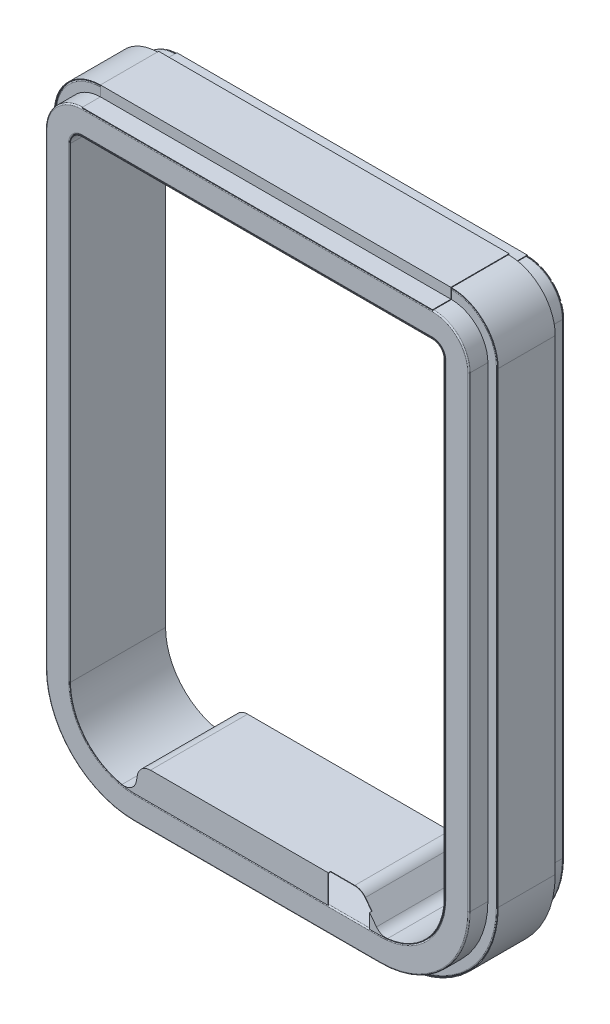
SolidWorks part; units mm, degrees
other "DetailItem1"
other "DetailItem2"
ref_plane "Front" through (0, 0, 0) normal (0, 0, 1) x (1, 0, 0)
ref_plane "Top" through (0, 0, 0) normal (0, 1, 0) x (1, 0, 0)
ref_plane "Right" through (0, 0, 0) normal (1, 0, 0) x (0, 0, -1)
sketch "Sketch15" plane through (0, 0, 0) normal (0, 0, 1) x (1, 0, 0)
  line L4 (3.9116, 60.0391) -> (3.9116, 11.1949)
  line L5 (41.8592, 61.3091) -> (5.1816, 61.3091)
  line L6 (43.1292, 11.1949) -> (43.1292, 60.0391)
  line L7 (10.6426, 4.4639) -> (36.3982, 4.4639)
  line L12 (1.3716, 11.1949) -> (1.3716, 60.0391)
  line L13 (36.3982, 1.9239) -> (10.6426, 1.9239)
  line L14 (45.6692, 60.0391) -> (45.6692, 11.1949)
  line L15 (5.1816, 63.8491) -> (41.8592, 63.8491)
  line L16 (23.5204, 61.3091) -> (23.5204, 4.4639) construction
  line L17 (23.5204, 32.8865) -> (13.0611, 32.8865) construction
  arc A4 (5.1816, 61.3091) -> (3.9116, 60.0391) centre (5.1816, 60.0391) ccw
  arc A5 (43.1292, 60.0391) -> (41.8592, 61.3091) centre (41.8592, 60.0391) ccw
  arc A6 (36.3982, 4.4639) -> (43.1292, 11.1949) centre (36.3982, 11.1949) ccw
  arc A7 (3.9116, 11.1949) -> (10.6426, 4.4639) centre (10.6426, 11.1949) ccw
  arc A12 (1.3716, 11.1949) -> (10.6426, 1.9239) centre (10.6426, 11.1949) ccw
  arc A13 (36.3982, 1.9239) -> (45.6692, 11.1949) centre (36.3982, 11.1949) ccw
  arc A14 (45.6692, 60.0391) -> (41.8592, 63.8491) centre (41.8592, 60.0391) ccw
  arc A15 (5.1816, 63.8491) -> (1.3716, 60.0391) centre (5.1816, 60.0391) ccw
  dimension "D1" = 1.27
  dimension "D2" = 6.731
  dimension "D3" = 2.54
  dimension "D4" = 23.5204
  dimension "D5" = 39.2176
  dimension "D6" = 56.8452
  dimension "D7" = 32.8865
extrude "Boss-Extrude4" add sketch "Sketch15" along normal blind 4.7244 and the other way blind 5.1816 separate body
ref_plane "Plane8" through (0, 0, 2.7432) normal (0, 0, 1) x (1, 0, 0)
sketch "Sketch16" plane through (0, 0, 2.7432) normal (0, 0, 1) x (1, 0, 0)
  line L8 (41.8592, 63.8491) -> (5.1816, 63.8491) construction
  line L9 (45.6692, 11.1949) -> (45.6692, 60.0391) construction
  line L10 (10.6426, 1.9239) -> (36.3982, 1.9239) construction
  line L11 (1.3716, 60.0391) -> (1.3716, 11.1949) construction
  line L12 (0.3556, 60.0391) -> (0.3556, 11.1949)
  line L13 (10.6426, 0.9079) -> (36.3982, 0.9079)
  line L14 (46.6852, 11.1949) -> (46.6852, 60.0391)
  line L15 (41.8592, 64.8651) -> (5.1816, 64.8651)
  line L16 (0.3556, 60.0391) -> (0.3556, 11.1949)
  line L17 (10.6426, 0.9079) -> (36.3982, 0.9079)
  line L18 (46.6852, 11.1949) -> (46.6852, 60.0391)
  line L19 (41.8592, 64.8651) -> (5.1816, 64.8651)
  line L20 (41.8592, 63.8491) -> (5.1816, 63.8491)
  line L21 (45.6692, 11.1949) -> (45.6692, 60.0391)
  line L22 (10.6426, 1.9239) -> (36.3982, 1.9239)
  line L23 (1.3716, 60.0391) -> (1.3716, 11.1949)
  arc A8 (45.6692, 60.0391) -> (41.8592, 63.8491) centre (41.8592, 60.0391) ccw construction
  arc A9 (36.3982, 1.9239) -> (45.6692, 11.1949) centre (36.3982, 11.1949) ccw construction
  arc A10 (1.3716, 11.1949) -> (10.6426, 1.9239) centre (10.6426, 11.1949) ccw construction
  arc A11 (5.1816, 63.8491) -> (1.3716, 60.0391) centre (5.1816, 60.0391) ccw construction
  arc A12 (5.1816, 64.8651) -> (0.3556, 60.0391) centre (5.1816, 60.0391) ccw
  arc A13 (0.3556, 11.1949) -> (10.6426, 0.9079) centre (10.6426, 11.1949) ccw
  arc A14 (36.3982, 0.9079) -> (46.6852, 11.1949) centre (36.3982, 11.1949) ccw
  arc A15 (46.6852, 60.0391) -> (41.8592, 64.8651) centre (41.8592, 60.0391) ccw
  arc A16 (5.1816, 64.8651) -> (0.3556, 60.0391) centre (5.1816, 60.0391) ccw
  arc A17 (0.3556, 11.1949) -> (10.6426, 0.9079) centre (10.6426, 11.1949) ccw
  arc A18 (36.3982, 0.9079) -> (46.6852, 11.1949) centre (36.3982, 11.1949) ccw
  arc A19 (46.6852, 60.0391) -> (41.8592, 64.8651) centre (41.8592, 60.0391) ccw
  arc A20 (45.6692, 60.0391) -> (41.8592, 63.8491) centre (41.8592, 60.0391) ccw
  arc A21 (36.3982, 1.9239) -> (45.6692, 11.1949) centre (36.3982, 11.1949) ccw
  arc A22 (1.3716, 11.1949) -> (10.6426, 1.9239) centre (10.6426, 11.1949) ccw
  arc A23 (5.1816, 63.8491) -> (1.3716, 60.0391) centre (5.1816, 60.0391) ccw
  dimension "D1" = 1.016
extrude "Boss-Extrude5" add sketch "Sketch16" against normal blind 5.969
fillet "Fillet1" radius 0.127 48 edges at (42.7572, 60.9372, -5.1816) (43.1292, 35.617, -5.1816) (41.1577, 6.4354, -5.1816) (23.5204, 4.4639, -5.1816) (5.8831, 6.4354, -5.1816) (3.9116, 35.617, -5.1816) (4.2836, 60.9372, -5.1816) (44.5533, 62.7332, -5.1816) (45.6692, 35.617, -5.1816) (42.9538, 4.6393, -5.1816) (23.5204, 1.9239, -5.1816) (4.087, 4.6393, -5.1816) (1.3716, 35.617, -5.1816) (2.4875, 62.7332, -5.1816) (45.2717, 63.4516, -3.2258) (46.6852, 35.617, -3.2258) (43.6722, 3.9209, -3.2258) (23.5204, 0.9079, -3.2258) (3.3686, 3.9209, -3.2258) (0.3556, 35.617, -3.2258) (1.7691, 63.4516, -3.2258) (45.2717, 63.4516, 2.7432) (46.6852, 35.617, 2.7432) (43.6722, 3.9209, 2.7432) (23.5204, 0.9079, 2.7432) (3.3686, 3.9209, 2.7432) (0.3556, 35.617, 2.7432) (1.7691, 63.4516, 2.7432) (42.7572, 60.9372, 4.7244) (43.1292, 35.617, 4.7244) (41.1577, 6.4354, 4.7244) (23.5204, 4.4639, 4.7244) (5.8831, 6.4354, 4.7244) (3.9116, 35.617, 4.7244) (4.2836, 60.9372, 4.7244) (44.5533, 62.7332, 4.7244) (45.6692, 35.617, 4.7244) (42.9538, 4.6393, 4.7244) (23.5204, 1.9239, 4.7244) (4.087, 4.6393, 4.7244) (1.3716, 35.617, 4.7244) (2.4875, 62.7332, 4.7244) (23.5204, 61.3091, -5.1816) (23.5204, 63.8491, -5.1816) (23.5204, 64.8651, -3.2258) (23.5204, 64.8651, 2.7432) (23.5204, 61.3091, 4.7244) (23.5204, 63.8491, 4.7244)
ref_plane "Plane1" through (0, 0, -1.8796) normal (0, 0, 1) x (1, 0, 0)
sketch "Sketch1" plane through (0, 0, -1.8796) normal (0, 0, 1) x (1, 0, 0)
  spline S0 degree 3 poles (23.5204, 0.7301) (4.8767, 0.6235) (10.288, 0.5536) (8.1184, 1.4309) knots 0 0 0 0 1 1 1 1
  dimension "D2" = 23.5204
ref_plane "Plane2" through (23.5204, 0.7301, -1.8796) normal (-1, -0.0057, 0) x (0, 0, 1)
sketch "Sketch2" plane through (23.5204, 0.7301, -1.8796) normal (-1, -0.0057, 0) x (0, 0, 1)
  line L2 (0.2921, -0.0762) -> (-0.2921, -0.0762)
  line L3 (0.2921, -0.0762) -> (0.2921, 0.0762)
  line L4 (0.2921, 0.0762) -> (-0.2921, 0.0762)
  line L5 (-0.2921, -0.0762) -> (-0.2921, 0.0762)
  line L6 (0.2921, -0.0762) -> (-0.2921, 0.0762) construction
  line L8 (0.2921, 0.0762) -> (-0.2921, -0.0762) construction
  point P0 (0, 0)
  dimension "D1" = 0.1524
  dimension "D2" = 0.5842
sweep "Sweep1" add profiles "Sketch2" path "Sketch1"
ref_plane "Plane5" [suppressed] through (33.274, 0, 0) normal (1, 0, 0) x (0, 0, -1)
ref_plane "Plane3" through (0, 0, -3.2512) normal (0, 0, 1) x (1, 0, 0)
sketch "Sketch3" plane through (0, 0, -3.2512) normal (0, 0, 1) x (1, 0, 0)
  line L3 (28.1912, 5.0643) -> (29.4725, 5.0643)
  arc A0 (29.4725, 5.0643) -> (31.7532, 4.7036) centre (29.4725, -2.3271) cw
  arc A1 (31.7532, 4.7036) -> (33.2691, 4.4639) centre (33.2691, 9.3766) ccw
ref_plane "Plane4" through (33.2691, 4.4639, -3.2512) normal (1, 0, 0) x (0, 0, -1)
sketch "Sketch4" plane through (33.2691, 0.758, 0.1016) normal (-1, 0, 0) x (0, 0, 1)
  line L1 (-3.6449, 3.7821) -> (-3.0607, 3.7821)
  line L2 (-3.6449, 3.7821) -> (-3.6449, 3.6297)
  line L3 (-3.6449, 3.6297) -> (-3.0607, 3.6297)
  line L4 (-3.0607, 3.7821) -> (-3.0607, 3.6297)
  line L5 (-3.6449, 3.7821) -> (-3.0607, 3.6297) construction
  line L6 (-3.6449, 3.6297) -> (-3.0607, 3.7821) construction
  point P0 (-3.3528, 3.7059)
  dimension "D1" = 0.5842
  dimension "D2" = 0.1524
sweep "Sweep2" add profiles "Sketch4" path "Sketch3"
sketch "Sketch6" [suppressed] plane through (0, 0, -5.0546) normal (0, 0, 1) x (1, 0, 0)
  line L0 (33.274, 4.4639) -> (32.3952, 4.4639)
  line L2 (29.0934, 7.7657) -> (29.0934, 8.5405)
  arc A0 (32.3952, 4.4639) -> (29.0934, 7.7657) centre (32.3952, 7.7657) cw
  dimension "D1" = 3.3018
sketch "Sketch7" [suppressed] plane through (33.274, 0, 0) normal (1, 0, 0) x (0, 0, -1)
  line L2 (5.0425, 4.3786) -> (4.4583, 4.3786)
  line L3 (5.0425, 4.3786) -> (5.0425, 4.531)
  line L4 (5.0425, 4.531) -> (4.4583, 4.531)
  line L5 (4.4583, 4.3786) -> (4.4583, 4.531)
  line L6 (5.0425, 4.3786) -> (4.4583, 4.531) construction
  line L7 (5.0425, 4.531) -> (4.4583, 4.3786) construction
  point P0 (4.7504, 4.4548)
  dimension "D1" = 0.5842
  dimension "D2" = 0.1524
sweep "Sweep4" [suppressed] add profiles "Sketch7" path "Sketch6"
sketch "Sketch8" [suppressed] plane through (0, 0, -1.8796) normal (0, 0, 1) x (1, 0, 0)
  line L0 (26.3291, -0.2377) -> (86.8426, -0.2377)
  arc A0 (10.6426, 0.9079) -> (13.2736, 0.7158) centre (10.643, -17.1973) cw
  arc A1 (13.2736, 0.7158) -> (26.3291, -0.2377) centre (26.3291, 89.6195) ccw
  dimension "D1" = 76.2
ref_plane "Plane6" [suppressed] through (10.6426, 0.9079, 2.6162) normal (1, 0, 0) x (0, 0, -1)
sketch "Sketch9" [suppressed] plane through (10.6426, 0.9079, 2.6162) normal (1, 0, 0) x (0, 0, -1)
  line L0 (5.715, -0.0006) -> (0, -0.0006) construction
  line L1 (1.5119, 0.2788) -> (0.9277, 0.2788)
  line L2 (1.5119, 0.2788) -> (1.5119, 0.1264)
  line L3 (1.5119, 0.1264) -> (0.9277, 0.1264)
  line L4 (0.9277, 0.2788) -> (0.9277, 0.1264)
  line L5 (1.5119, 0.2788) -> (0.9277, 0.1264) construction
  line L6 (1.5119, 0.1264) -> (0.9277, 0.2788) construction
  point P0 (1.2198, 0.2026)
  dimension "D1" = 0.5842
  dimension "D2" = 0.1524
  dimension "D3" = 0.2032
sweep "Sweep5" [suppressed] add profiles "Sketch9" path "Sketch8"
sketch "Sketch10" plane through (0, 0, 4.7244) normal (0, 0, 1) x (1, 0, 0)
  line L0 (12.3423, 7.4248) -> (33.4766, 7.4248)
  line L1 (10.9685, 6.2812) -> (10.6426, 4.5147)
  line L2 (36.3982, 4.5147) -> (34.585, 6.8781)
  line L3 (36.3731, 4.464) -> (34.5447, 6.8472)
  line L4 (12.3423, 7.374) -> (33.4766, 7.374)
  line L5 (11.0185, 6.272) -> (10.6849, 4.4641)
  line L6 (11.0185, 6.272) -> (10.6926, 4.5055) construction
  line L8 (41.8592, 61.3091) -> (5.1816, 61.3091) construction
  line L9 (43.1292, 11.1949) -> (43.1292, 60.0391) construction
  line L11 (3.9116, 60.0391) -> (3.9116, 11.1949) construction
  line L12 (3.9624, 60.0391) -> (3.9624, 11.1949)
  line L13 (10.6426, 4.5147) -> (36.3982, 4.5147)
  line L14 (43.0784, 11.1949) -> (43.0784, 60.0391)
  line L15 (41.8592, 61.2583) -> (5.1816, 61.2583)
  line L16 (3.9624, 60.0391) -> (3.9624, 11.1949)
  line L18 (43.0784, 11.1949) -> (43.0784, 60.0391)
  line L19 (41.8592, 61.2583) -> (5.1816, 61.2583)
  line L20 (41.8592, 61.3091) -> (5.1816, 61.3091)
  line L21 (43.1292, 11.1949) -> (43.1292, 60.0391)
  line L22 (36.3579, 4.4838) -> (34.5447, 6.8472) construction
  line L23 (3.9116, 60.0391) -> (3.9116, 11.1949)
  arc A0 (12.3423, 7.4248) -> (10.9685, 6.2812) centre (12.3423, 6.0278) ccw
  arc A1 (33.4766, 7.4248) -> (34.585, 6.8781) centre (33.4766, 6.0278) cw
  arc A2 (33.4766, 7.374) -> (34.5447, 6.8472) centre (33.4766, 6.0278) cw
  arc A3 (12.3423, 7.374) -> (11.0185, 6.272) centre (12.3423, 6.0278) ccw
  arc A8 (43.1292, 60.0391) -> (41.8592, 61.3091) centre (41.8592, 60.0391) ccw construction
  arc A9 (36.3982, 4.4639) -> (43.1292, 11.1949) centre (36.3982, 11.1949) ccw construction
  arc A10 (3.9116, 11.1949) -> (10.6426, 4.4639) centre (10.6426, 11.1949) ccw construction
  arc A11 (5.1816, 61.3091) -> (3.9116, 60.0391) centre (5.1816, 60.0391) ccw construction
  arc A12 (5.1816, 61.2583) -> (3.9624, 60.0391) centre (5.1816, 60.0391) ccw
  arc A13 (3.9624, 11.1949) -> (10.6426, 4.5147) centre (10.6426, 11.1949) ccw
  arc A14 (36.3982, 4.5147) -> (43.0784, 11.1949) centre (36.3982, 11.1949) ccw
  arc A15 (43.0784, 60.0391) -> (41.8592, 61.2583) centre (41.8592, 60.0391) ccw
  arc A16 (5.1816, 61.2583) -> (3.9624, 60.0391) centre (5.1816, 60.0391) ccw
  arc A17 (3.9624, 11.1949) -> (10.6426, 4.5147) centre (10.6426, 11.1949) ccw
  arc A18 (36.3982, 4.5147) -> (43.0784, 11.1949) centre (36.3982, 11.1949) ccw
  arc A19 (43.0784, 60.0391) -> (41.8592, 61.2583) centre (41.8592, 60.0391) ccw
  arc A20 (43.1292, 60.0391) -> (41.8592, 61.3091) centre (41.8592, 60.0391) ccw
  arc A21 (36.3731, 4.464) -> (43.1292, 11.1949) centre (36.3982, 11.1949) ccw
  arc A22 (3.9116, 11.1949) -> (10.6849, 4.4641) centre (10.6426, 11.1949) ccw
  arc A23 (5.1816, 61.3091) -> (3.9116, 60.0391) centre (5.1816, 60.0391) ccw
  dimension "D2" = 1.397
  dimension "D4" = 7.374
  dimension "D1" = 0.0508
  dimension "D3" = 0.0508
extrude "Boss-Extrude1" add sketch "Sketch10" against normal blind 9.906 separate body
sketch "Sketch11" plane through (0, 0, 2.7432) normal (0, 0, 1) x (1, 0, 0)
  line L8 (5.1816, 64.8651) -> (41.8592, 64.8651) construction
  line L9 (0.3556, 11.1949) -> (0.3556, 60.0391) construction
  line L10 (36.3982, 0.9079) -> (10.6426, 0.9079) construction
  line L11 (46.6852, 60.0391) -> (46.6852, 11.1949) construction
  line L12 (46.7487, 11.1949) -> (46.7487, 60.0391)
  line L13 (10.6426, 0.8444) -> (36.3982, 0.8444)
  line L14 (0.2921, 60.0391) -> (0.2921, 11.1949)
  line L15 (41.8592, 64.9286) -> (5.1816, 64.9286)
  line L16 (46.7487, 11.1949) -> (46.7487, 60.0391)
  line L17 (10.6426, 0.8444) -> (36.3982, 0.8444)
  line L18 (0.2921, 60.0391) -> (0.2921, 11.1949)
  line L19 (41.8592, 64.9286) -> (5.1816, 64.9286)
  line L20 (5.1816, 64.8651) -> (41.8592, 64.8651)
  line L21 (0.3556, 11.1949) -> (0.3556, 60.0391)
  line L22 (36.3982, 0.9079) -> (10.6426, 0.9079)
  line L23 (46.6852, 60.0391) -> (46.6852, 11.1949)
  arc A8 (5.1816, 64.8651) -> (0.3556, 60.0391) centre (5.1816, 60.0391) ccw construction
  arc A9 (0.3556, 11.1949) -> (10.6426, 0.9079) centre (10.6426, 11.1949) ccw construction
  arc A10 (36.3982, 0.9079) -> (46.6852, 11.1949) centre (36.3982, 11.1949) ccw construction
  arc A11 (46.6852, 60.0391) -> (41.8592, 64.8651) centre (41.8592, 60.0391) ccw construction
  arc A12 (46.7487, 60.0391) -> (41.8592, 64.9286) centre (41.8592, 60.0391) ccw
  arc A13 (36.3982, 0.8444) -> (46.7487, 11.1949) centre (36.3982, 11.1949) ccw
  arc A14 (0.2921, 11.1949) -> (10.6426, 0.8444) centre (10.6426, 11.1949) ccw
  arc A15 (5.1816, 64.9286) -> (0.2921, 60.0391) centre (5.1816, 60.0391) ccw
  arc A16 (46.7487, 60.0391) -> (41.8592, 64.9286) centre (41.8592, 60.0391) ccw
  arc A17 (36.3982, 0.8444) -> (46.7487, 11.1949) centre (36.3982, 11.1949) ccw
  arc A18 (0.2921, 11.1949) -> (10.6426, 0.8444) centre (10.6426, 11.1949) ccw
  arc A19 (5.1816, 64.9286) -> (0.2921, 60.0391) centre (5.1816, 60.0391) ccw
  arc A20 (5.1816, 64.8651) -> (0.3556, 60.0391) centre (5.1816, 60.0391) ccw
  arc A21 (0.3556, 11.1949) -> (10.6426, 0.9079) centre (10.6426, 11.1949) ccw
  arc A22 (36.3982, 0.9079) -> (46.6852, 11.1949) centre (36.3982, 11.1949) ccw
  arc A23 (46.6852, 60.0391) -> (41.8592, 64.8651) centre (41.8592, 60.0391) ccw
  dimension "D1" = 0.0635
extrude "Boss-Extrude2" add sketch "Sketch11" against normal blind 5.969 separate body
sketch "Sketch12" plane through (0, 0, -5.1816) normal (0, 0, -1) x (-1, 0, 0)
  line L0 (-10.6426, 4.5147) -> (-10.9685, 6.2812) construction
  line L1 (-12.3423, 7.4248) -> (-33.4766, 7.4248) construction
  line L2 (-34.585, 6.8781) -> (-36.3982, 4.5147) construction
  line L3 (-10.6426, 4.5147) -> (-10.9685, 6.2812)
  line L4 (-12.3423, 7.4248) -> (-33.4766, 7.4248)
  line L5 (-34.585, 6.8781) -> (-36.3982, 4.5147)
  line L7 (-13.6987, 3.3028) -> (-33.3421, 3.3028)
  line L8 (-41.8592, 61.2583) -> (-5.1816, 61.2583) construction
  line L9 (-43.0784, 11.1949) -> (-43.0784, 60.0391) construction
  line L11 (-3.9624, 60.0391) -> (-3.9624, 11.1949) construction
  line L16 (-1.4224, 11.1949) -> (-1.4224, 60.0391)
  line L17 (-36.3982, 1.9747) -> (-34.361, 1.9747)
  line L18 (-45.6184, 60.0391) -> (-45.6184, 11.1949)
  line L19 (-5.1816, 63.7983) -> (-41.8592, 63.7983)
  line L20 (-41.8592, 61.2583) -> (-5.1816, 61.2583)
  line L21 (-43.0784, 11.1949) -> (-43.0784, 60.0391)
  line L22 (-23.5204, 1.0349) -> (-23.5204, 4.8815) construction
  line L23 (-3.9624, 60.0391) -> (-3.9624, 11.1949)
  line L24 (-36.3982, 1.0349) -> (-10.6426, 1.0349) construction
  line L28 (-34.361, 1.9747) -> (-33.3421, 3.3028)
  line L29 (-12.6798, 1.9747) -> (-13.6987, 3.3028)
  line L30 (-10.6426, 1.9747) -> (-12.6798, 1.9747)
  arc A0 (-10.9685, 6.2812) -> (-12.3423, 7.4248) centre (-12.3423, 6.0278) ccw construction
  arc A1 (-33.4766, 7.4248) -> (-34.585, 6.8781) centre (-33.4766, 6.0278) ccw construction
  arc A2 (-10.9685, 6.2812) -> (-12.3423, 7.4248) centre (-12.3423, 6.0278) ccw
  arc A3 (-33.4766, 7.4248) -> (-34.585, 6.8781) centre (-33.4766, 6.0278) ccw
  arc A8 (-41.8592, 61.2583) -> (-43.0784, 60.0391) centre (-41.8592, 60.0391) ccw construction
  arc A9 (-43.0784, 11.1949) -> (-36.3982, 4.5147) centre (-36.3982, 11.1949) ccw construction
  arc A10 (-10.6426, 4.5147) -> (-3.9624, 11.1949) centre (-10.6426, 11.1949) ccw construction
  arc A11 (-3.9624, 60.0391) -> (-5.1816, 61.2583) centre (-5.1816, 60.0391) ccw construction
  arc A16 (-1.4224, 60.0391) -> (-5.1816, 63.7983) centre (-5.1816, 60.0391) ccw
  arc A17 (-10.6426, 1.9747) -> (-1.4224, 11.1949) centre (-10.6426, 11.1949) ccw
  arc A18 (-45.6184, 11.1949) -> (-36.3982, 1.9747) centre (-36.3982, 11.1949) ccw
  arc A19 (-41.8592, 63.7983) -> (-45.6184, 60.0391) centre (-41.8592, 60.0391) ccw
  arc A20 (-41.8592, 61.2583) -> (-43.0784, 60.0391) centre (-41.8592, 60.0391) ccw
  arc A21 (-43.0784, 11.1949) -> (-36.3982, 4.5147) centre (-36.3982, 11.1949) ccw
  arc A22 (-10.6426, 4.5147) -> (-3.9624, 11.1949) centre (-10.6426, 11.1949) ccw
  arc A23 (-3.9624, 60.0391) -> (-5.1816, 61.2583) centre (-5.1816, 60.0391) ccw
extrude "Boss-Extrude3" add sketch "Sketch12" along normal blind 0.254
sketch "Sketch13" plane through (0, 0, -5.4356) normal (0, 0, -1) x (-1, 0, 0)
  line L0 (-41.8592, 60.0391) -> (-42.9953, 63.6225)
  line L2 (-41.8592, 60.0391) -> (-43.2706, 63.5233)
  line L3 (-41.8592, 60.0391) -> (-44.3277, 62.8742)
  line L4 (-41.8592, 60.0391) -> (-44.4687, 62.7451)
  line L5 (-41.8592, 60.0391) -> (-45.3349, 61.4713)
  line L6 (-41.8592, 60.0391) -> (-45.4154, 61.2576)
  line L7 (-23.5204, 61.2583) -> (-23.5204, 43.5667) construction
  line L9 (-5.1816, 60.0391) -> (-1.6254, 61.2576)
  line L10 (-5.1816, 60.0391) -> (-1.7059, 61.4713)
  line L11 (-5.1816, 60.0391) -> (-2.5721, 62.7451)
  line L12 (-5.1816, 60.0391) -> (-2.7131, 62.8742)
  line L13 (-5.1816, 60.0391) -> (-3.7702, 63.5233)
  line L14 (-5.1816, 60.0391) -> (-4.0455, 63.6225)
  arc A0 (-41.8592, 63.7983) -> (-45.6184, 60.0391) centre (-41.8592, 60.0391) ccw construction
  arc A1 (-41.8592, 63.7983) -> (-45.6184, 60.0391) centre (-41.8592, 60.0391) ccw
  circle A4 centre (-41.8592, 60.0391) radius 1.3647
  circle A5 centre (-5.1816, 60.0391) radius 1.3647
  arc A6 (-5.1816, 63.7983) -> (-1.4224, 60.0391) centre (-5.1816, 60.0391) cw
extrude "Cut-Extrude1" cut sketch "Sketch13" against normal blind 0.254
ref_plane "Plane7" through (23.5204, 0, 0) normal (-1, 0, 0) x (0, 0, 1)
sketch "Sketch14" plane through (23.5204, 0.7301, 1.397) normal (-1, 0, 0) x (0, 0, 1)
  line L0 (-4.6228, 64.1985) -> (1.3462, 64.1985)
  line L1 (1.3462, 59.309) -> (1.3462, 64.1985) construction
  line L2 (1.3462, 64.1985) -> (1.3462, 63.119)
  line L4 (1.3462, 63.119) -> (3.2004, 63.119) construction
  line L5 (1.3462, 63.119) -> (3.3274, 63.119)
  line L6 (-4.6228, 64.1985) -> (-4.6228, 59.309) construction
  line L7 (-4.6228, 64.1985) -> (-4.6228, 63.119)
  line L8 (-4.6228, 63.119) -> (-6.5916, 63.119)
  line L11 (-4.6228, 64.1985) -> (1.3462, 64.1985) construction
extrude "Extrude-Thin1" add sketch "Sketch14" along normal mid plane 36.6776 separate body thin thin type one direction reverse wall 0.0635
fillet "Fillet2" [suppressed] radius 0.127
ref_plane "coil midplane" [suppressed] through (0, 32.8865, 0) normal (0, 1, 0) x (1, 0, 0)
sketch "Sketch17" [suppressed] plane through (0, 0, 4.7244) normal (0, 0, 1) x (1, 0, 0)
  line L0 (41.8592, 63.8491) -> (5.1816, 63.8491) construction
  line L1 (45.6692, 11.1949) -> (45.6692, 60.0391) construction
  line L2 (10.6426, 1.9239) -> (36.3982, 1.9239) construction
  line L3 (1.3716, 60.0391) -> (1.3716, 11.1949) construction
  line L4 (41.8592, 63.8491) -> (5.1816, 63.8491)
  line L5 (45.6692, 11.1949) -> (45.6692, 60.0391)
  line L6 (10.6426, 1.9239) -> (36.3982, 1.9239)
  line L7 (1.3716, 60.0391) -> (1.3716, 11.1949)
  arc A0 (45.6692, 60.0391) -> (41.8592, 63.8491) centre (41.8592, 60.0391) ccw construction
  arc A1 (36.3982, 1.9239) -> (45.6692, 11.1949) centre (36.3982, 11.1949) ccw construction
  arc A2 (1.3716, 11.1949) -> (10.6426, 1.9239) centre (10.6426, 11.1949) ccw construction
  arc A3 (5.1816, 63.8491) -> (1.3716, 60.0391) centre (5.1816, 60.0391) ccw construction
  arc A4 (45.6692, 60.0391) -> (41.8592, 63.8491) centre (41.8592, 60.0391) ccw
  arc A5 (36.3982, 1.9239) -> (45.6692, 11.1949) centre (36.3982, 11.1949) ccw
  arc A6 (1.3716, 11.1949) -> (10.6426, 1.9239) centre (10.6426, 11.1949) ccw
  arc A7 (5.1816, 63.8491) -> (1.3716, 60.0391) centre (5.1816, 60.0391) ccw
sketch "Sketch19" [suppressed] plane through (0, 0, 2.7432) normal (0, 0, 1) x (1, 0, 0)
  line L0 (5.1816, 64.8651) -> (41.8592, 64.8651) construction
  line L1 (0.3556, 11.1949) -> (0.3556, 60.0391) construction
  line L2 (36.3982, 0.9079) -> (10.6426, 0.9079) construction
  line L3 (46.6852, 60.0391) -> (46.6852, 11.1949) construction
  line L4 (5.1816, 64.8651) -> (41.8592, 64.8651)
  line L5 (0.3556, 11.1949) -> (0.3556, 60.0391)
  line L6 (36.3982, 0.9079) -> (10.6426, 0.9079)
  line L7 (46.6852, 60.0391) -> (46.6852, 11.1949)
  line L12 (5.1816, 64.7127) -> (41.8592, 64.7127)
  line L13 (0.508, 11.1949) -> (0.508, 60.0391)
  line L14 (36.3982, 1.0603) -> (10.6426, 1.0603)
  line L15 (46.5328, 60.0391) -> (46.5328, 11.1949)
  arc A0 (5.1816, 64.8651) -> (0.3556, 60.0391) centre (5.1816, 60.0391) ccw construction
  arc A1 (0.3556, 11.1949) -> (10.6426, 0.9079) centre (10.6426, 11.1949) ccw construction
  arc A2 (36.3982, 0.9079) -> (46.6852, 11.1949) centre (36.3982, 11.1949) ccw construction
  arc A3 (46.6852, 60.0391) -> (41.8592, 64.8651) centre (41.8592, 60.0391) ccw construction
  arc A4 (5.1816, 64.8651) -> (0.3556, 60.0391) centre (5.1816, 60.0391) ccw
  arc A5 (0.3556, 11.1949) -> (10.6426, 0.9079) centre (10.6426, 11.1949) ccw
  arc A6 (36.3982, 0.9079) -> (46.6852, 11.1949) centre (36.3982, 11.1949) ccw
  arc A7 (46.6852, 60.0391) -> (41.8592, 64.8651) centre (41.8592, 60.0391) ccw
  arc A12 (46.5328, 60.0391) -> (41.8592, 64.7127) centre (41.8592, 60.0391) ccw
  arc A13 (5.1816, 64.7127) -> (0.508, 60.0391) centre (5.1816, 60.0391) ccw
  arc A14 (0.508, 11.1949) -> (10.6426, 1.0603) centre (10.6426, 11.1949) ccw
  arc A15 (36.3982, 1.0603) -> (46.5328, 11.1949) centre (36.3982, 11.1949) ccw
  dimension "D1" = 0.1524
extrude "Cut-Extrude3" [suppressed] cut sketch "Sketch19" against normal through all
sketch "Sketch18" [suppressed] plane through (0, 0, 4.7244) normal (0, 0, 1) x (1, 0, 0)
  line L4 (45.6692, 11.1949) -> (45.6692, 60.0391) construction
  line L5 (10.6426, 1.9239) -> (36.3982, 1.9239) construction
  line L6 (1.3716, 60.0391) -> (1.3716, 11.1949) construction
  line L7 (41.8592, 63.8491) -> (5.1816, 63.8491) construction
  line L12 (45.6692, 11.1949) -> (45.6692, 60.0391)
  line L13 (10.6426, 1.9239) -> (36.3982, 1.9239)
  line L14 (1.3716, 60.0391) -> (1.3716, 11.1949)
  line L15 (41.8592, 63.8491) -> (5.1816, 63.8491)
  line L20 (41.8592, 63.6967) -> (5.1816, 63.6967)
  line L21 (1.524, 60.0391) -> (1.524, 11.1949)
  line L22 (10.6426, 2.0763) -> (36.3982, 2.0763)
  line L23 (45.5168, 11.1949) -> (45.5168, 60.0391)
  line L24 (41.8592, 63.6967) -> (5.1816, 63.6967)
  line L25 (1.524, 60.0391) -> (1.524, 11.1949)
  line L26 (10.6426, 2.0763) -> (36.3982, 2.0763)
  line L27 (45.5168, 11.1949) -> (45.5168, 60.0391)
  arc A4 (45.6692, 60.0391) -> (41.8592, 63.8491) centre (41.8592, 60.0391) ccw construction
  arc A5 (36.3982, 1.9239) -> (45.6692, 11.1949) centre (36.3982, 11.1949) ccw construction
  arc A6 (1.3716, 11.1949) -> (10.6426, 1.9239) centre (10.6426, 11.1949) ccw construction
  arc A7 (5.1816, 63.8491) -> (1.3716, 60.0391) centre (5.1816, 60.0391) ccw construction
  arc A12 (45.6692, 60.0391) -> (41.8592, 63.8491) centre (41.8592, 60.0391) ccw
  arc A13 (36.3982, 1.9239) -> (45.6692, 11.1949) centre (36.3982, 11.1949) ccw
  arc A14 (1.3716, 11.1949) -> (10.6426, 1.9239) centre (10.6426, 11.1949) ccw
  arc A15 (5.1816, 63.8491) -> (1.3716, 60.0391) centre (5.1816, 60.0391) ccw
  arc A20 (5.1816, 63.6967) -> (1.524, 60.0391) centre (5.1816, 60.0391) ccw
  arc A21 (1.524, 11.1949) -> (10.6426, 2.0763) centre (10.6426, 11.1949) ccw
  arc A22 (36.3982, 2.0763) -> (45.5168, 11.1949) centre (36.3982, 11.1949) ccw
  arc A23 (45.5168, 60.0391) -> (41.8592, 63.6967) centre (41.8592, 60.0391) ccw
  arc A24 (5.1816, 63.6967) -> (1.524, 60.0391) centre (5.1816, 60.0391) ccw
  arc A25 (1.524, 11.1949) -> (10.6426, 2.0763) centre (10.6426, 11.1949) ccw
  arc A26 (36.3982, 2.0763) -> (45.5168, 11.1949) centre (36.3982, 11.1949) ccw
  arc A27 (45.5168, 60.0391) -> (41.8592, 63.6967) centre (41.8592, 60.0391) ccw
  dimension "D1" = 0.1524
extrude "Cut-Extrude2" [suppressed] cut sketch "Sketch18" against normal up to surface (1.9812 mm away)
sketch "Sketch20" [suppressed] plane through (0, 0, -5.1816) normal (0, 0, -1) x (-1, 0, 0)
  line L0 (-10.6426, 1.9239) -> (-36.3982, 1.9239) construction
  line L1 (-1.3716, 60.0391) -> (-1.3716, 11.1949) construction
  line L2 (-41.8592, 63.8491) -> (-5.1816, 63.8491) construction
  line L3 (-45.6692, 11.1949) -> (-45.6692, 60.0391) construction
  line L4 (-10.6426, 1.9239) -> (-36.3982, 1.9239)
  line L5 (-1.3716, 60.0391) -> (-1.3716, 11.1949)
  line L6 (-41.8592, 63.8491) -> (-5.1816, 63.8491)
  line L7 (-45.6692, 11.1949) -> (-45.6692, 60.0391)
  line L16 (-1.524, 11.1949) -> (-1.524, 60.0391)
  line L17 (-36.3982, 2.0763) -> (-10.6426, 2.0763)
  line L18 (-45.5168, 60.0391) -> (-45.5168, 11.1949)
  line L19 (-5.1816, 63.6967) -> (-41.8592, 63.6967)
  line L20 (-1.524, 11.1949) -> (-1.524, 60.0391)
  line L21 (-36.3982, 2.0763) -> (-10.6426, 2.0763)
  line L22 (-45.5168, 60.0391) -> (-45.5168, 11.1949)
  line L23 (-5.1816, 63.6967) -> (-41.8592, 63.6967)
  arc A0 (-45.6692, 11.1949) -> (-36.3982, 1.9239) centre (-36.3982, 11.1949) ccw construction
  arc A1 (-10.6426, 1.9239) -> (-1.3716, 11.1949) centre (-10.6426, 11.1949) ccw construction
  arc A2 (-1.3716, 60.0391) -> (-5.1816, 63.8491) centre (-5.1816, 60.0391) ccw construction
  arc A3 (-41.8592, 63.8491) -> (-45.6692, 60.0391) centre (-41.8592, 60.0391) ccw construction
  arc A4 (-45.6692, 11.1949) -> (-36.3982, 1.9239) centre (-36.3982, 11.1949) ccw
  arc A5 (-10.6426, 1.9239) -> (-1.3716, 11.1949) centre (-10.6426, 11.1949) ccw
  arc A6 (-1.3716, 60.0391) -> (-5.1816, 63.8491) centre (-5.1816, 60.0391) ccw
  arc A7 (-41.8592, 63.8491) -> (-45.6692, 60.0391) centre (-41.8592, 60.0391) ccw
  arc A16 (-1.524, 60.0391) -> (-5.1816, 63.6967) centre (-5.1816, 60.0391) ccw
  arc A17 (-10.6426, 2.0763) -> (-1.524, 11.1949) centre (-10.6426, 11.1949) ccw
  arc A18 (-45.5168, 11.1949) -> (-36.3982, 2.0763) centre (-36.3982, 11.1949) ccw
  arc A19 (-41.8592, 63.6967) -> (-45.5168, 60.0391) centre (-41.8592, 60.0391) ccw
  arc A20 (-1.524, 60.0391) -> (-5.1816, 63.6967) centre (-5.1816, 60.0391) ccw
  arc A21 (-10.6426, 2.0763) -> (-1.524, 11.1949) centre (-10.6426, 11.1949) ccw
  arc A22 (-45.5168, 11.1949) -> (-36.3982, 2.0763) centre (-36.3982, 11.1949) ccw
  arc A23 (-41.8592, 63.6967) -> (-45.5168, 60.0391) centre (-41.8592, 60.0391) ccw
  dimension "D1" = 0.1524
extrude "Cut-Extrude4" [suppressed] cut sketch "Sketch20" against normal up to surface (1.9558 mm away)
sketch "Sketch21" [suppressed] plane through (0, 0, -3.2258) normal (0, 0, -1) x (-1, 0, 0)
  line L0 (-41.8592, 64.8651) -> (-5.1816, 64.8651) construction
  line L1 (-46.6852, 11.1949) -> (-46.6852, 60.0391) construction
  line L2 (-10.6426, 0.9079) -> (-36.3982, 0.9079) construction
  line L3 (-0.3556, 60.0391) -> (-0.3556, 11.1949) construction
  line L4 (-41.8592, 64.8651) -> (-5.1816, 64.8651)
  line L5 (-46.6852, 11.1949) -> (-46.6852, 60.0391)
  line L6 (-10.6426, 0.9079) -> (-36.3982, 0.9079)
  line L7 (-0.3556, 60.0391) -> (-0.3556, 11.1949)
  line L8 (-41.8592, 63.8491) -> (-5.1816, 63.8491) construction
  line L9 (-45.6692, 11.1949) -> (-45.6692, 60.0391) construction
  line L10 (-10.6426, 1.9239) -> (-36.3982, 1.9239) construction
  line L11 (-1.3716, 60.0391) -> (-1.3716, 11.1949) construction
  line L12 (-41.8592, 63.8491) -> (-5.1816, 63.8491)
  line L13 (-45.6692, 11.1949) -> (-45.6692, 60.0391)
  line L14 (-10.6426, 1.9239) -> (-36.3982, 1.9239)
  line L15 (-1.3716, 60.0391) -> (-1.3716, 11.1949)
  arc A0 (-41.8592, 64.8651) -> (-46.6852, 60.0391) centre (-41.8592, 60.0391) ccw construction
  arc A1 (-46.6852, 11.1949) -> (-36.3982, 0.9079) centre (-36.3982, 11.1949) ccw construction
  arc A2 (-10.6426, 0.9079) -> (-0.3556, 11.1949) centre (-10.6426, 11.1949) ccw construction
  arc A3 (-0.3556, 60.0391) -> (-5.1816, 64.8651) centre (-5.1816, 60.0391) ccw construction
  arc A4 (-41.8592, 64.8651) -> (-46.6852, 60.0391) centre (-41.8592, 60.0391) ccw
  arc A5 (-46.6852, 11.1949) -> (-36.3982, 0.9079) centre (-36.3982, 11.1949) ccw
  arc A6 (-10.6426, 0.9079) -> (-0.3556, 11.1949) centre (-10.6426, 11.1949) ccw
  arc A7 (-0.3556, 60.0391) -> (-5.1816, 64.8651) centre (-5.1816, 60.0391) ccw
  arc A8 (-41.8592, 63.8491) -> (-45.6692, 60.0391) centre (-41.8592, 60.0391) ccw construction
  arc A9 (-45.6692, 11.1949) -> (-36.3982, 1.9239) centre (-36.3982, 11.1949) ccw construction
  arc A10 (-10.6426, 1.9239) -> (-1.3716, 11.1949) centre (-10.6426, 11.1949) ccw construction
  arc A11 (-1.3716, 60.0391) -> (-5.1816, 63.8491) centre (-5.1816, 60.0391) ccw construction
  arc A12 (-41.8592, 63.8491) -> (-45.6692, 60.0391) centre (-41.8592, 60.0391) ccw
  arc A13 (-45.6692, 11.1949) -> (-36.3982, 1.9239) centre (-36.3982, 11.1949) ccw
  arc A14 (-10.6426, 1.9239) -> (-1.3716, 11.1949) centre (-10.6426, 11.1949) ccw
  arc A15 (-1.3716, 60.0391) -> (-5.1816, 63.8491) centre (-5.1816, 60.0391) ccw
fillet "Fillet4" [suppressed] radius 0.127
fillet "Fillet6" radius 1.27 2 edges at (36.3982, 4.5147, -0.3556) (10.6426, 4.5147, -0.3556)
fillet "Fillet7" radius 1.27 4 edges at (13.6987, 3.3028, -5.3086) (12.6798, 1.9747, -5.3086) (34.361, 1.9747, -5.3086) (33.3421, 3.3028, -5.3086)
sketch "Sketch22" plane through (0, 0, -5.4356) normal (0, 0, -1) x (-1, 0, 0)
  line L0 (-3.9624, 11.1949) -> (-3.9624, 60.0391) construction
  line L1 (-5.1816, 61.2583) -> (-41.8592, 61.2583) construction
  line L2 (-43.0784, 60.0391) -> (-43.0784, 11.1949) construction
  line L5 (-3.9624, 11.1949) -> (-3.9624, 60.0391)
  line L6 (-5.1816, 61.2583) -> (-41.8592, 61.2583)
  line L7 (-43.0784, 60.0391) -> (-43.0784, 11.1949)
  line L10 (-9.3603, 4.639) -> (-9.3603, 2.0643)
  line L11 (-37.1399, 4.556) -> (-37.1399, 2.0046)
  line L20 (-13.3174, 2.8058) -> (-13.0611, 2.4717)
  line L21 (-12.0534, 1.9747) -> (-10.6426, 1.9747)
  line L22 (-1.4224, 11.1949) -> (-1.4224, 60.0391)
  line L23 (-1.6254, 61.2576) -> (-3.8906, 60.4815)
  line L24 (-3.9199, 60.559) -> (-1.7059, 61.4713)
  line L25 (-2.5721, 62.7451) -> (-4.2343, 61.0214)
  line L26 (-4.2855, 61.0683) -> (-2.7131, 62.8742)
  line L27 (-3.7702, 63.5233) -> (-4.6692, 61.3039)
  line L28 (-4.7692, 61.34) -> (-4.0455, 63.6225)
  line L29 (-5.1816, 63.7983) -> (-41.8592, 63.7983)
  line L30 (-42.9953, 63.6225) -> (-42.2716, 61.34)
  line L31 (-42.3716, 61.3039) -> (-43.2706, 63.5233)
  line L32 (-44.3277, 62.8742) -> (-42.7553, 61.0683)
  line L33 (-42.8065, 61.0214) -> (-44.4687, 62.7451)
  line L34 (-45.3349, 61.4713) -> (-43.1209, 60.559)
  line L35 (-43.1502, 60.4815) -> (-45.4154, 61.2576)
  line L36 (-45.6184, 60.0391) -> (-45.6184, 11.1949)
  line L37 (-36.3982, 1.9747) -> (-34.9874, 1.9747)
  line L38 (-33.9797, 2.4717) -> (-33.7234, 2.8058)
  line L39 (-32.7158, 3.3028) -> (-14.325, 3.3028)
  line L42 (-1.4224, 11.1949) -> (-1.4224, 60.0391)
  line L43 (-1.6254, 61.2576) -> (-3.8906, 60.4815)
  line L44 (-3.9199, 60.559) -> (-1.7059, 61.4713)
  line L45 (-2.5721, 62.7451) -> (-4.2343, 61.0214)
  line L46 (-4.2855, 61.0683) -> (-2.7131, 62.8742)
  line L47 (-3.7702, 63.5233) -> (-4.6692, 61.3039)
  line L48 (-4.7692, 61.34) -> (-4.0455, 63.6225)
  line L49 (-5.1816, 63.7983) -> (-41.8592, 63.7983)
  line L50 (-42.9953, 63.6225) -> (-42.2716, 61.34)
  line L51 (-42.3716, 61.3039) -> (-43.2706, 63.5233)
  line L52 (-44.3277, 62.8742) -> (-42.7553, 61.0683)
  line L53 (-42.8065, 61.0214) -> (-44.4687, 62.7451)
  line L54 (-45.3349, 61.4713) -> (-43.1209, 60.559)
  line L55 (-43.1502, 60.4815) -> (-45.4154, 61.2576)
  line L56 (-45.6184, 60.0391) -> (-45.6184, 11.1949)
  arc A1 (-9.3603, 4.639) -> (-3.9624, 11.1949) centre (-10.6426, 11.1949) ccw construction
  arc A2 (-3.9624, 60.0391) -> (-5.1816, 61.2583) centre (-5.1816, 60.0391) ccw construction
  arc A3 (-41.8592, 61.2583) -> (-43.0784, 60.0391) centre (-41.8592, 60.0391) ccw construction
  arc A4 (-43.0784, 11.1949) -> (-37.1399, 4.556) centre (-36.3982, 11.1949) ccw construction
  arc A9 (-9.3603, 4.639) -> (-3.9624, 11.1949) centre (-10.6426, 11.1949) ccw
  arc A10 (-3.9624, 60.0391) -> (-5.1816, 61.2583) centre (-5.1816, 60.0391) ccw
  arc A11 (-41.8592, 61.2583) -> (-43.0784, 60.0391) centre (-41.8592, 60.0391) ccw
  arc A12 (-43.0784, 11.1949) -> (-37.1399, 4.556) centre (-36.3982, 11.1949) ccw
  arc A16 (-10.6426, 1.9747) -> (-1.4224, 11.1949) centre (-10.6426, 11.1949) ccw construction
  arc A20 (-13.0611, 2.4717) -> (-12.0534, 1.9747) centre (-12.0534, 3.2447) ccw
  arc A21 (-10.6426, 1.9747) -> (-1.4224, 11.1949) centre (-10.6426, 11.1949) ccw
  arc A22 (-1.4224, 60.0391) -> (-1.6254, 61.2576) centre (-5.1816, 60.0391) ccw
  arc A23 (-3.8906, 60.4815) -> (-3.9199, 60.559) centre (-5.1816, 60.0391) ccw
  arc A24 (-1.7059, 61.4713) -> (-2.5721, 62.7451) centre (-5.1816, 60.0391) ccw
  arc A25 (-4.2343, 61.0214) -> (-4.2855, 61.0683) centre (-5.1816, 60.0391) ccw
  arc A26 (-2.7131, 62.8742) -> (-3.7702, 63.5233) centre (-5.1816, 60.0391) ccw
  arc A27 (-4.6692, 61.3039) -> (-4.7692, 61.34) centre (-5.1816, 60.0391) ccw
  arc A28 (-4.0455, 63.6225) -> (-5.1816, 63.7983) centre (-5.1816, 60.0391) ccw
  arc A29 (-41.8592, 63.7983) -> (-42.9953, 63.6225) centre (-41.8592, 60.0391) ccw
  arc A30 (-42.2716, 61.34) -> (-42.3716, 61.3039) centre (-41.8592, 60.0391) ccw
  arc A31 (-43.2706, 63.5233) -> (-44.3277, 62.8742) centre (-41.8592, 60.0391) ccw
  arc A32 (-42.7553, 61.0683) -> (-42.8065, 61.0214) centre (-41.8592, 60.0391) ccw
  arc A33 (-44.4687, 62.7451) -> (-45.3349, 61.4713) centre (-41.8592, 60.0391) ccw
  arc A34 (-43.1209, 60.559) -> (-43.1502, 60.4815) centre (-41.8592, 60.0391) ccw
  arc A35 (-45.4154, 61.2576) -> (-45.6184, 60.0391) centre (-41.8592, 60.0391) ccw
  arc A36 (-45.6184, 11.1949) -> (-36.3982, 1.9747) centre (-36.3982, 11.1949) ccw
  arc A37 (-34.9874, 1.9747) -> (-33.9797, 2.4717) centre (-34.9874, 3.2447) ccw
  arc A38 (-32.7158, 3.3028) -> (-33.7234, 2.8058) centre (-32.7158, 2.0328) ccw
  arc A39 (-13.3174, 2.8058) -> (-14.325, 3.3028) centre (-14.325, 2.0328) ccw
  arc A41 (-9.3603, 2.0643) -> (-1.4224, 11.1949) centre (-10.6426, 11.1949) ccw
  arc A42 (-1.4224, 60.0391) -> (-1.6254, 61.2576) centre (-5.1816, 60.0391) ccw
  arc A43 (-3.8906, 60.4815) -> (-3.9199, 60.559) centre (-5.1816, 60.0391) ccw
  arc A44 (-1.7059, 61.4713) -> (-2.5721, 62.7451) centre (-5.1816, 60.0391) ccw
  arc A45 (-4.2343, 61.0214) -> (-4.2855, 61.0683) centre (-5.1816, 60.0391) ccw
  arc A46 (-2.7131, 62.8742) -> (-3.7702, 63.5233) centre (-5.1816, 60.0391) ccw
  arc A47 (-4.6692, 61.3039) -> (-4.7692, 61.34) centre (-5.1816, 60.0391) ccw
  arc A48 (-4.0455, 63.6225) -> (-5.1816, 63.7983) centre (-5.1816, 60.0391) ccw
  arc A49 (-41.8592, 63.7983) -> (-42.9953, 63.6225) centre (-41.8592, 60.0391) ccw
  arc A50 (-42.2716, 61.34) -> (-42.3716, 61.3039) centre (-41.8592, 60.0391) ccw
  arc A51 (-43.2706, 63.5233) -> (-44.3277, 62.8742) centre (-41.8592, 60.0391) ccw
  arc A52 (-42.7553, 61.0683) -> (-42.8065, 61.0214) centre (-41.8592, 60.0391) ccw
  arc A53 (-44.4687, 62.7451) -> (-45.3349, 61.4713) centre (-41.8592, 60.0391) ccw
  arc A54 (-43.1209, 60.559) -> (-43.1502, 60.4815) centre (-41.8592, 60.0391) ccw
  arc A55 (-45.4154, 61.2576) -> (-45.6184, 60.0391) centre (-41.8592, 60.0391) ccw
  arc A56 (-45.6184, 11.1949) -> (-37.1399, 2.0046) centre (-36.3982, 11.1949) ccw
  dimension "D1" = 0
extrude "Cut-Extrude5" cut sketch "Sketch22" against normal blind 0.2032
fillet "Fillet11" radius 1.3208 2 edges at (36.3731, 4.464, -0.2286) (10.6849, 4.4641, -0.2286)
sketch "Sketch24" plane through (0, 0, -5.1816) normal (0, 0, 1) x (1, 0, 0)
  line L0 (12.3423, 7.374) -> (33.4766, 7.374) construction
  line L1 (34.5447, 6.8472) -> (35.951, 5.0142) construction
  line L2 (12.3423, 7.374) -> (33.4766, 7.374)
  line L3 (34.5447, 6.8472) -> (35.951, 5.0142)
  line L4 (9.4111, 4.5787) -> (9.4111, 2.0573)
  line L5 (37.0891, 4.5005) -> (37.0891, 1.9747)
  line L6 (9.3603, 4.639) -> (9.3603, 2.0643) construction
  line L7 (37.1399, 2.0046) -> (37.1399, 4.556) construction
  line L8 (10.9029, 5.6457) -> (11.0185, 6.272) construction
  line L9 (10.9029, 5.6457) -> (11.0185, 6.272)
  line L20 (10.6426, 1.9747) -> (12.0534, 1.9747)
  line L21 (13.0611, 2.4717) -> (13.3174, 2.8058)
  line L22 (14.325, 3.3028) -> (32.7158, 3.3028)
  line L23 (33.7234, 2.8058) -> (33.9797, 2.4717)
  line L24 (34.9874, 1.9747) -> (36.3982, 1.9747)
  line L25 (45.6184, 11.1949) -> (45.6184, 60.0391)
  line L26 (45.4154, 61.2576) -> (43.1502, 60.4815)
  line L27 (43.1209, 60.559) -> (45.3349, 61.4713)
  line L28 (44.4687, 62.7451) -> (42.8065, 61.0214)
  line L29 (42.7553, 61.0683) -> (44.3277, 62.8742)
  line L30 (43.2706, 63.5233) -> (42.3716, 61.3039)
  line L31 (42.2716, 61.34) -> (42.9953, 63.6225)
  line L32 (41.8592, 63.7983) -> (5.1816, 63.7983)
  line L33 (4.0455, 63.6225) -> (4.7692, 61.34)
  line L34 (4.6692, 61.3039) -> (3.7702, 63.5233)
  line L35 (2.7131, 62.8742) -> (4.2855, 61.0683)
  line L36 (4.2343, 61.0214) -> (2.5721, 62.7451)
  line L37 (1.7059, 61.4713) -> (3.9199, 60.559)
  line L38 (3.8906, 60.4815) -> (1.6254, 61.2576)
  line L39 (1.4224, 60.0391) -> (1.4224, 11.1949)
  line L40 (10.6426, 1.9747) -> (12.0534, 1.9747)
  line L41 (13.0611, 2.4717) -> (13.3174, 2.8058)
  line L42 (14.325, 3.3028) -> (32.7158, 3.3028)
  line L43 (33.7234, 2.8058) -> (33.9797, 2.4717)
  line L44 (34.9874, 1.9747) -> (37.0891, 1.9747)
  arc A1 (12.3423, 7.374) -> (11.0185, 6.272) centre (12.3423, 6.0278) ccw construction
  arc A2 (9.3505, 4.5891) -> (10.9029, 5.6457) centre (9.604, 5.8853) ccw construction
  arc A3 (34.5447, 6.8472) -> (33.4766, 7.374) centre (33.4766, 6.0278) ccw construction
  arc A4 (35.951, 5.0142) -> (37.1455, 4.5055) centre (36.9989, 5.8182) ccw construction
  arc A6 (12.3423, 7.374) -> (11.0185, 6.272) centre (12.3423, 6.0278) ccw
  arc A8 (9.4111, 4.5787) -> (10.9029, 5.6457) centre (9.604, 5.8853) ccw
  arc A9 (34.5447, 6.8472) -> (33.4766, 7.374) centre (33.4766, 6.0278) ccw
  arc A10 (35.951, 5.0142) -> (37.0891, 4.5005) centre (36.9989, 5.8182) ccw
  arc A20 (12.0534, 1.9747) -> (13.0611, 2.4717) centre (12.0534, 3.2447) ccw
  arc A21 (14.325, 3.3028) -> (13.3174, 2.8058) centre (14.325, 2.0328) ccw
  arc A22 (33.7234, 2.8058) -> (32.7158, 3.3028) centre (32.7158, 2.0328) ccw
  arc A23 (33.9797, 2.4717) -> (34.9874, 1.9747) centre (34.9874, 3.2447) ccw
  arc A24 (36.3982, 1.9747) -> (45.6184, 11.1949) centre (36.3982, 11.1949) ccw
  arc A25 (45.6184, 60.0391) -> (45.4154, 61.2576) centre (41.8592, 60.0391) ccw
  arc A26 (43.1502, 60.4815) -> (43.1209, 60.559) centre (41.8592, 60.0391) ccw
  arc A27 (45.3349, 61.4713) -> (44.4687, 62.7451) centre (41.8592, 60.0391) ccw
  arc A28 (42.8065, 61.0214) -> (42.7553, 61.0683) centre (41.8592, 60.0391) ccw
  arc A29 (44.3277, 62.8742) -> (43.2706, 63.5233) centre (41.8592, 60.0391) ccw
  arc A30 (42.3716, 61.3039) -> (42.2716, 61.34) centre (41.8592, 60.0391) ccw
  arc A31 (42.9953, 63.6225) -> (41.8592, 63.7983) centre (41.8592, 60.0391) ccw
  arc A32 (5.1816, 63.7983) -> (4.0455, 63.6225) centre (5.1816, 60.0391) ccw
  arc A33 (4.7692, 61.34) -> (4.6692, 61.3039) centre (5.1816, 60.0391) ccw
  arc A34 (3.7702, 63.5233) -> (2.7131, 62.8742) centre (5.1816, 60.0391) ccw
  arc A35 (4.2855, 61.0683) -> (4.2343, 61.0214) centre (5.1816, 60.0391) ccw
  arc A36 (2.5721, 62.7451) -> (1.7059, 61.4713) centre (5.1816, 60.0391) ccw
  arc A37 (3.9199, 60.559) -> (3.8906, 60.4815) centre (5.1816, 60.0391) ccw
  arc A38 (1.6254, 61.2576) -> (1.4224, 60.0391) centre (5.1816, 60.0391) ccw
  arc A39 (1.4224, 11.1949) -> (10.6426, 1.9747) centre (10.6426, 11.1949) ccw
  arc A40 (12.0534, 1.9747) -> (13.0611, 2.4717) centre (12.0534, 3.2447) ccw
  arc A41 (14.325, 3.3028) -> (13.3174, 2.8058) centre (14.325, 2.0328) ccw
  arc A42 (33.7234, 2.8058) -> (32.7158, 3.3028) centre (32.7158, 2.0328) ccw
  arc A43 (33.9797, 2.4717) -> (34.9874, 1.9747) centre (34.9874, 3.2447) ccw
  arc A59 (9.4111, 2.0573) -> (10.6426, 1.9747) centre (10.6426, 11.1949) ccw
  dimension "D2" = 0.0508
  dimension "D3" = 0.0508
  dimension "D1" = 0
extrude "Cut-Extrude6" cut sketch "Sketch24" against normal blind 0.1778
fillet "Fillet9" radius 1.27 2 edges at (37.1399, 3.2803, -5.2324) (9.3603, 3.3516, -5.2324)
fillet "Fillet10" radius 1.27 2 edges at (9.3603, 3.3516, -5.4356) (37.1399, 3.2803, -5.4356)
fillet "Fillet12" radius 1.3208 2 edges at (37.0891, 3.2506, -5.3594) (9.4111, 3.318, -5.3594)
fillet "Fillet13" radius 1.3208 2 edges at (9.4111, 3.318, -5.1816) (37.0891, 3.2506, -5.1816)
sketch "Sketch25" plane through (0, 7.4248, 0) normal (0, 1, 0) x (1, 0, 0)
  line L0 (12.3423, -4.7244) -> (33.4766, -4.7244) construction
  line L1 (30.4463, -4.7244) -> (35.2182, -4.7244)
  line L2 (30.4463, -4.7244) -> (30.4463, -4.462)
  line L3 (30.4463, -4.462) -> (35.2182, -4.462)
  line L4 (35.2182, -4.7244) -> (35.2182, -4.462)
  line L5 (34.2319, -4.462) -> (31.7319, -4.462) construction
sketch "Sketch26" plane through (0, 0, 2.7432) normal (0, 0, 1) x (1, 0, 0)
  line L0 (10.6426, 0.8444) -> (36.3982, 0.8444) construction
  line L1 (10.6426, 0.8444) -> (33.557, 0.8444)
  line L2 (10.6426, 0.4888) -> (29.8615, 0.4888)
  line L3 (29.8615, 0.4888) -> (33.557, 0.8444)
  line L4 (8.765, 0.6548) -> (7.5762, 1.3091)
  line L6 (10.6426, 0.8444) -> (36.3982, 0.8444) construction
  line L7 (10.6426, 0.4888) -> (36.3982, 0.4888) construction
  arc A1 (0.2921, 11.1949) -> (10.6426, 0.8444) centre (10.6426, 11.1949) ccw construction
  arc A2 (8.765, 0.6548) -> (10.6426, 0.4888) centre (10.6426, 11.1949) ccw
  arc A3 (7.5762, 1.3091) -> (10.6426, 0.8444) centre (10.6426, 11.1949) ccw
  arc A5 (0.2921, 11.1949) -> (10.6426, 0.8444) centre (10.6426, 11.1949) ccw construction
  arc A6 (-0.0635, 11.1949) -> (10.6426, 0.4888) centre (10.6426, 11.1949) ccw construction
  dimension "D1" = 0.3556
extrude "Boss-Extrude6" add sketch "Sketch26" against normal up to surface (5.969 mm away) up to face at (23.5204, 33.969, -3.2258)
fillet "Fillet15" radius 1.3208 4 edges at (7.5762, 1.3091, -0.2413) (8.765, 0.6548, -0.2413) (33.557, 0.8444, -0.2413) (29.8615, 0.4888, -0.2413)
sketch "Sketch28" plane through (0, 0, 4.7244) normal (0, 0, 1) x (1, 0, 0)
  line L0 (33.4766, 7.374) -> (12.3423, 7.374) construction
  line L1 (35.951, 5.0142) -> (34.5447, 6.8472) construction
  line L2 (33.4766, 7.374) -> (12.3423, 7.374)
  line L3 (35.951, 5.0142) -> (34.5447, 6.8472)
  line L4 (10.6426, 4.4639) -> (36.3982, 4.4639) construction
  line L5 (10.6426, 4.4639) -> (36.3982, 4.4639)
  line L6 (10.9029, 5.6457) -> (11.0185, 6.272) construction
  line L7 (10.9029, 5.6457) -> (11.0185, 6.272)
  arc A0 (9.3505, 4.5891) -> (10.9029, 5.6457) centre (9.604, 5.8853) ccw construction
  arc A2 (34.5447, 6.8472) -> (33.4766, 7.374) centre (33.4766, 6.0278) ccw construction
  arc A3 (35.951, 5.0142) -> (36.4272, 4.6275) centre (36.9989, 5.8182) ccw construction
  arc A4 (36.4272, 4.6275) -> (36.9036, 4.5008) centre (36.9989, 5.8182) ccw construction
  arc A5 (9.3505, 4.5891) -> (10.9029, 5.6457) centre (9.604, 5.8853) ccw
  arc A6 (12.3423, 7.374) -> (11.0185, 6.272) centre (12.3423, 6.0278) ccw
  arc A7 (34.5447, 6.8472) -> (33.4766, 7.374) centre (33.4766, 6.0278) ccw
  arc A8 (35.951, 5.0142) -> (36.4272, 4.6275) centre (36.9989, 5.8182) ccw
  arc A9 (36.4272, 4.6275) -> (37.1455, 4.5055) centre (36.9989, 5.8182) ccw
  arc A10 (36.3982, 4.4639) -> (43.1292, 11.1949) centre (36.3982, 11.1949) ccw construction
  arc A11 (3.9116, 11.1949) -> (10.6426, 4.4639) centre (10.6426, 11.1949) ccw construction
  arc A12 (36.3982, 4.4639) -> (37.1455, 4.5055) centre (36.3982, 11.1949) ccw
  arc A13 (9.3505, 4.5891) -> (10.6426, 4.4639) centre (10.6426, 11.1949) ccw
  arc A14 (12.3423, 7.374) -> (11.0185, 6.272) centre (12.3423, 6.0278) ccw construction
extrude "Boss-Extrude7" add sketch "Sketch28" against normal blind 0.0508
sketch "Sketch29" plane through (0, 0, 4.7244) normal (0, 0, 1) x (1, 0, 0)
  line L0 (12.3423, 7.4248) -> (33.4766, 7.4248) construction
  line L1 (30.9435, 7.4248) -> (35.2723, 7.4248)
  line L2 (30.9435, 7.4248) -> (30.9435, 4.4639)
  line L3 (30.9435, 4.4639) -> (35.2723, 4.4639)
  line L4 (35.2723, 7.4248) -> (35.2723, 4.4639)
  line L5 (10.6426, 4.4639) -> (36.3982, 4.4639) construction
extrude "Cut-Extrude8" cut sketch "Sketch29" against normal blind 0.254
sketch "Sketch30" [suppressed] plane through (29.1605, 0, 0) normal (1, 0, 0) x (0, 0, -1)
  line L0 (6.4516, 80.6639) -> (6.4516, 42.3046)
  line L1 (5.0425, 8.5405) -> (5.0425, 11.3146)
  line L2 (5.0546, 4.4639) -> (-4.5974, 4.4639) construction
  arc A0 (5.0425, 11.3146) -> (5.7471, 26.8096) centre (175.785, 11.3146) cw
  arc A1 (5.7471, 26.8096) -> (6.4516, 42.3046) centre (-164.2908, 42.3046) ccw
  dimension "D1" = 76.2
  dimension "D2" = 1.27
  dimension "D3" = 2.7741
sketch "Sketch31" [suppressed] plane through (0, 8.5405, 0) normal (0, 1, 0) x (1, 0, 0)
  line L4 (29.0081, 4.4583) -> (29.1605, 4.4583)
  line L5 (29.1605, 4.4583) -> (29.1605, 5.0425)
  line L6 (29.1605, 5.0425) -> (29.0081, 5.0425)
  line L7 (29.0081, 5.0425) -> (29.0081, 4.4583)
  line L8 (29.0081, 4.4583) -> (29.1605, 4.4583)
  line L9 (29.1605, 4.4583) -> (29.1605, 5.0425)
  line L10 (29.1605, 5.0425) -> (29.0081, 5.0425)
  line L11 (29.0081, 5.0425) -> (29.0081, 4.4583)
  dimension "D1" = 0
sweep "Sweep6" [suppressed] add profiles "Sketch31" path "Sketch30"
